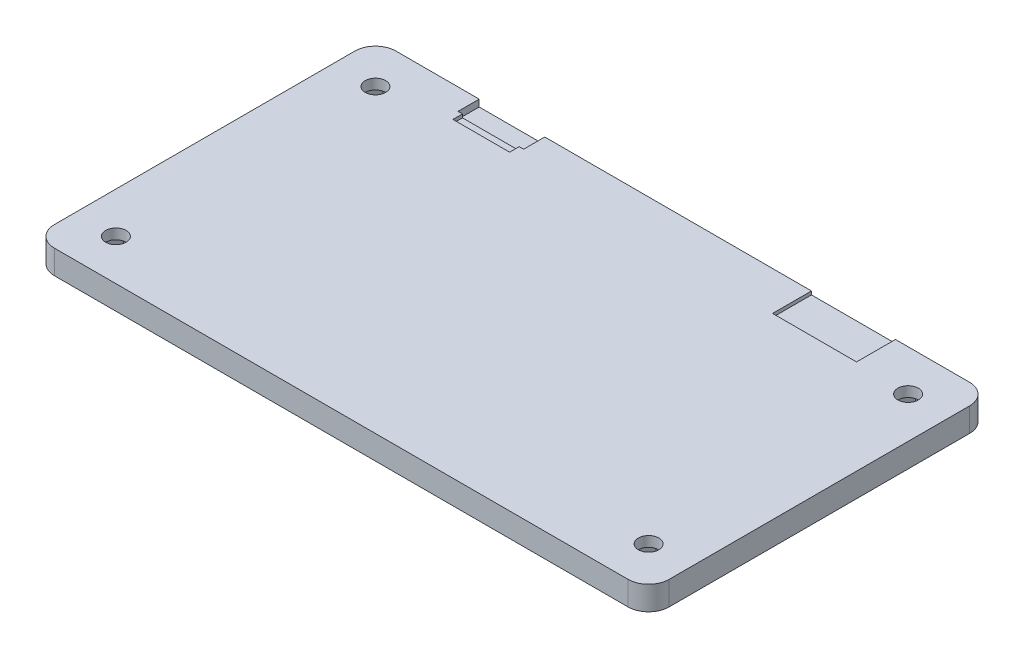
SolidWorks part; units mm, degrees
ref_plane "前视基准面" through (0, 0, 0) normal (0, 0, 1) x (1, 0, 0)
ref_plane "上视基准面" through (0, 0, 0) normal (0, 1, 0) x (1, 0, 0)
ref_plane "右视基准面" through (0, 0, 0) normal (1, 0, 0) x (0, 0, -1)
other "Configuration Table"
sketch "草图1" plane through (0, 0, 0) normal (0, 1, 0) x (1, 0, 0)
  line L1 (-42, -25) -> (42, -25)
  line L2 (-45, -22) -> (-45, 22)
  line L3 (-42, 25) -> (42, 25)
  line L4 (45, -22) -> (45, 22)
  line L5 (-45, -25) -> (45, 25) construction
  line L6 (-45, 25) -> (45, -25) construction
  arc A0 (-42, -25) -> (-45, -22) centre (-42, -22) cw
  arc A1 (45, -22) -> (42, -25) centre (42, -22) cw
  arc A2 (45, 22) -> (42, 25) centre (42, 22) ccw
  arc A3 (-45, 22) -> (-42, 25) centre (-42, 22) cw
  circle A4 centre (-39, 19) radius 1.5
  circle A5 centre (39, 19) radius 1.5
  circle A6 centre (-39, -19) radius 1.5
  circle A7 centre (39, -19) radius 1.5
  point P0 (0, 0)
  dimension "D3" = 3
  dimension "D4" = 3
  dimension "D1" = 90
  dimension "D2" = 50
  dimension "D5" = 6
  dimension "D6" = 6
  dimension "D7" = 6
  dimension "D8" = 6
extrude "凸台-拉伸1" add sketch "草图1" along normal blind 3.5
sketch "草图2" plane through (0, 3.5, 0) normal (0, 1, 0) x (1, 0, 0)
  line L1 (-29.8, 25) -> (-20.2, 25)
  line L2 (-29.8, 25) -> (-29.8, 21.9)
  line L3 (-29.8, 21.9) -> (-20.2, 21.9)
  line L4 (-20.2, 25) -> (-20.2, 21.9)
  line L7 (-29.15, 20.5) -> (-20.85, 20.5)
  line L8 (-29.15, 20.5) -> (-29.15, 21.9)
  line L9 (-29.15, 21.9) -> (-20.85, 21.9)
  line L10 (-20.85, 20.5) -> (-20.85, 21.9)
  line L12 (18.85, 19.3) -> (31.15, 19.3)
  line L13 (18.85, 19.3) -> (18.85, 25)
  line L14 (18.85, 25) -> (31.15, 25)
  line L15 (31.15, 19.3) -> (31.15, 25)
extrude "切除-拉伸1" cut sketch "草图2" against normal blind 0.5 contours L12 L15 L14 L13 | L7 L10 L9 L8
extrude "切除-拉伸2" cut sketch "草图2<3>" against normal blind 1 contours L4 L3 L2 L1
sketch "草图2<3>" plane through (0, 3.5, 0) normal (0, 1, 0) x (1, 0, 0) same geometry as "草图2"
sketch "草图3" plane through (0, 0, 0) normal (0, -1, 0) x (1, 0, 0)
  line L1 (-37.4989, 21.6) -> (-40.5011, 21.6)
  line L2 (-40.5011, 21.6) -> (-42.0022, 19)
  line L3 (-42.0022, 19) -> (-40.5011, 16.4)
  line L4 (-40.5011, 16.4) -> (-37.4989, 16.4)
  line L5 (-37.4989, 16.4) -> (-35.9978, 19)
  line L6 (-35.9978, 19) -> (-37.4989, 21.6)
  line L7 (-37.4989, -16.4) -> (-40.5011, -16.4)
  line L8 (-40.5011, -16.4) -> (-42.0022, -19)
  line L9 (-42.0022, -19) -> (-40.5011, -21.6)
  line L10 (-40.5011, -21.6) -> (-37.4989, -21.6)
  line L11 (-37.4989, -21.6) -> (-35.9978, -19)
  line L12 (-35.9978, -19) -> (-37.4989, -16.4)
  line L13 (40.5011, -16.4) -> (37.4989, -16.4)
  line L14 (37.4989, -16.4) -> (35.9978, -19)
  line L15 (35.9978, -19) -> (37.4989, -21.6)
  line L16 (37.4989, -21.6) -> (40.5011, -21.6)
  line L17 (40.5011, -21.6) -> (42.0022, -19)
  line L18 (42.0022, -19) -> (40.5011, -16.4)
  line L19 (37.4989, 21.6) -> (35.9978, 19)
  line L20 (35.9978, 19) -> (37.4989, 16.4)
  line L21 (37.4989, 16.4) -> (40.5011, 16.4)
  line L22 (40.5011, 16.4) -> (42.0022, 19)
  line L23 (42.0022, 19) -> (40.5011, 21.6)
  line L24 (40.5011, 21.6) -> (37.4989, 21.6)
  circle A0 centre (-39, 19) radius 2.6 construction
  circle A1 centre (-39, -19) radius 2.6 construction
  circle A2 centre (39, -19) radius 2.6 construction
  circle A3 centre (39, 19) radius 2.6 construction
  dimension "D1" = 5.2
extrude "切除-拉伸3" cut sketch "草图3" against normal blind 2
